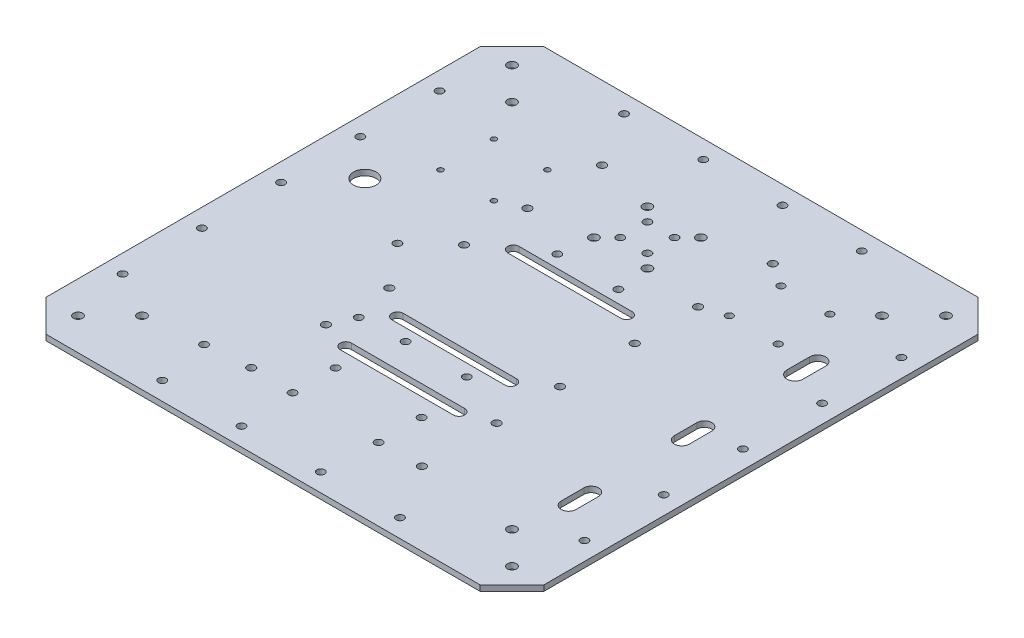
SolidWorks part; units mm, degrees
ref_plane "Front Plane" through (0, 0, 0) normal (0, 0, 1) x (1, 0, 0)
ref_plane "Top Plane" through (0, 0, 0) normal (0, 1, 0) x (1, 0, 0)
ref_plane "Right Plane" through (0, 0, 0) normal (1, 0, 0) x (0, 0, -1)
sketch "Sketch1" plane through (0, 0, 0) normal (0, 1, 0) x (1, 0, 0)
  line L0 (-160.4847, 61.5307) -> (-142.5242, 79.4912)
  line L1 (-160.4847, 79.4912) -> (118.9153, 79.4912)
  line L2 (-160.4847, 79.4912) -> (-160.4847, -199.9088)
  line L3 (-160.4847, -199.9088) -> (118.9153, -199.9088)
  line L4 (118.9153, 79.4912) -> (118.9153, -199.9088)
  line L5 (-20.7847, 79.4912) -> (-20.7847, -199.9088) construction
  line L6 (-160.4847, -60.2088) -> (118.9153, -60.2088) construction
  line L7 (118.9153, 61.5307) -> (100.9548, 79.4912)
  line L8 (118.9153, -181.9483) -> (100.9548, -199.9088)
  line L9 (-160.4847, -181.9483) -> (-142.5242, -199.9088)
  line L10 (-268.2478, 187.2542) -> (226.6783, -307.6719) construction
  line L11 (226.6783, -307.6719) -> (226.6783, 187.2542) construction
  line L12 (226.6783, 187.2542) -> (-268.2478, -307.6719) construction
  line L13 (-268.2478, -307.6719) -> (-268.2478, 187.2542) construction
  line L14 (-268.2478, 187.2542) -> (226.6783, 187.2542) construction
  line L15 (-268.2478, -307.6719) -> (226.6783, -307.6719) construction
  line L16 (-151.5045, 70.5109) -> (-268.2478, 187.2542) construction
  point P8 (-20.7847, 79.4912)
  point P11 (-160.4847, -60.2088)
  point P19 (118.9153, -60.2088)
  point P20 (-20.7847, -199.9088)
  point P22 (-151.5045, 70.5109)
  point P25 (-20.7847, -60.2088)
  point P26 (-20.7847, -60.2088)
  dimension "D1" = 279.4
  dimension "D2" = 279.4
  dimension "D3" = 165.1
  dimension "D4" = 25.4
extrude "Boss-Extrude1" add sketch "Sketch1" along normal blind 3.175 contours L2 L9 L3 L8 L4 L7 L1 L0 region at (-20.7847, 0, 60.2088)
sketch "Sketch2" plane through (0, 3.175, 0) normal (0, 1, 0) x (1, 0, 0)
  line L0 (-20.7847, 79.4912) -> (-20.7847, -287.8465) construction
  line L1 (-142.5242, 79.4912) -> (100.9548, 79.4912) construction
  line L2 (118.9153, -60.2088) -> (-158.2106, -60.2088) construction
  line L3 (118.9153, 61.5307) -> (118.9153, -181.9483) construction
  circle A0 centre (-38.0567, -17.5368) radius 2.159
  circle A1 centre (-3.7667, -17.5368) radius 2.159
  circle A2 centre (-38.0567, -102.6268) radius 2.159
  circle A3 centre (-3.7667, -102.6268) radius 2.159
  dimension "D5" = 4.318
  dimension "D6" = 4.318
  dimension "D7" = 4.318
  dimension "D8" = 4.318
  dimension "D1" = 17.272
  dimension "D2" = 34.29
  dimension "D3" = 85.09
  dimension "D4" = 42.672
extrude "Cut-Extrude1" cut sketch "Sketch2" against normal through all
sketch "Sketch4" plane through (0, 3.175, 0) normal (0, 1, 0) x (1, 0, 0)
  line L0 (-52.5347, -27.7088) -> (10.9653, -27.7088) construction
  line L1 (-52.5347, -24.5338) -> (10.9653, -24.5338)
  line L2 (-52.5347, -30.8838) -> (10.9653, -30.8838)
  line L3 (-52.5347, -92.7088) -> (10.9653, -92.7088) construction
  line L4 (-52.5347, -89.5338) -> (10.9653, -89.5338)
  line L5 (-52.5347, -95.8838) -> (10.9653, -95.8838)
  line L6 (118.9153, 61.5307) -> (118.9153, -181.9483) construction
  line L7 (-20.7847, -92.7088) -> (-20.7847, -198.1921) construction
  line L8 (-160.4847, -60.2088) -> (118.9153, -60.2088) construction
  line L9 (-160.4847, 61.5307) -> (-160.4847, -181.9483) construction
  line L14 (-52.5347, -121.708) -> (10.9653, -121.708) construction
  line L15 (-52.5347, -118.533) -> (10.9653, -118.533)
  line L16 (-52.5347, -124.883) -> (10.9653, -124.883)
  line L17 (-20.7847, -27.7088) -> (-20.7847, -92.7088) construction
  arc A0 (-52.5347, -24.5338) -> (-52.5347, -30.8838) centre (-52.5347, -27.7088) ccw
  arc A1 (10.9653, -30.8838) -> (10.9653, -24.5338) centre (10.9653, -27.7088) ccw
  arc A2 (-52.5347, -89.5338) -> (-52.5347, -95.8838) centre (-52.5347, -92.7088) ccw
  arc A3 (10.9653, -95.8838) -> (10.9653, -89.5338) centre (10.9653, -92.7088) ccw
  arc A7 (-52.5347, -118.533) -> (-52.5347, -124.883) centre (-52.5347, -121.708) ccw
  arc A8 (10.9653, -124.883) -> (10.9653, -118.533) centre (10.9653, -121.708) ccw
  point P2 (-20.7847, -27.7088)
  point P7 (-20.7847, -92.7088)
  point P18 (-20.7847, -60.2088)
  point P19 (-20.7847, -60.2088)
  point P33 (-20.7847, -121.708)
  dimension "D1" = 63.5
  dimension "D2" = 63.5
  dimension "D3" = 6.35
  dimension "D4" = 6.35
  dimension "D5" = 65
  dimension "D6" = 28.9992
  dimension "D8" = 63.5
  dimension "D9" = 6.35
extrude "Cut-Extrude2" cut sketch "Sketch4" against normal through all
sketch "Sketch7" plane through (0, 3.175, 0) normal (0, 1, 0) x (1, 0, 0)
  line L0 (-96.7307, 89.5196) -> (-96.7307, -24.0818) construction
  line L1 (-160.4847, -60.2088) -> (118.9153, -60.2088) construction
  line L2 (-160.4847, 61.5307) -> (-160.4847, -181.9483) construction
  line L3 (118.9153, 61.5307) -> (118.9153, -181.9483) construction
  line L4 (-20.7847, 79.4912) -> (-20.7847, -252.674) construction
  line L5 (-142.5242, 79.4912) -> (100.9548, 79.4912) construction
  circle A0 centre (-81.7447, 20.5632) radius 1.524
  circle A1 centre (-81.7447, -9.4088) radius 1.524
  circle A2 centre (-111.7167, -9.4088) radius 1.524
  circle A3 centre (-111.7167, 20.5632) radius 1.524
  dimension "D1" = 3.048
  dimension "D2" = 14.986
  dimension "D4" = 29.972
  dimension "D3" = 3.048
  dimension "D5" = 50.8
  dimension "D6" = 60.96
  dimension "D7" = 14.986
extrude "Cut-Extrude3" cut sketch "Sketch7" against normal through all
sketch "Sketch8" plane through (0, 3.175, 0) normal (0, 1, 0) x (1, 0, 0)
  line L0 (-142.5242, -199.9088) -> (100.9548, -199.9088) construction
  line L1 (118.9153, 61.5307) -> (118.9153, -181.9483) construction
  circle A0 centre (8.4253, -175.0168) radius 1.524
  circle A1 centre (8.4253, -144.5368) radius 1.524
  circle A2 centre (32.3013, -175.0168) radius 1.524
  circle A3 centre (32.3013, -144.5368) radius 1.524
  dimension "D1" = 3.048
  dimension "D2" = 30.48
  dimension "D3" = 23.876
  dimension "D4" = 24.892
  dimension "D5" = 86.614
extrude "Cut-Extrude4" [suppressed] cut sketch "Sketch8" against normal through all and the other way through all
sketch "Sketch10" plane through (0, 0, 0) normal (0, -1, 0) x (1, 0, 0)
  line L0 (-142.5242, 199.9088) -> (100.9548, 199.9088) construction
  line L1 (-20.7847, 199.9088) -> (-20.7847, 128.7119) construction
  line L2 (-52.5347, 124.883) -> (10.9653, 124.883) construction
  circle A0 centre (-44.9147, 159.173) radius 2.159
  circle A1 centre (3.3453, 159.173) radius 2.159
  circle A2 centre (-44.9147, 135.043) radius 2.159
  circle A3 centre (3.3453, 135.043) radius 2.159
  dimension "D1" = 4.318
  dimension "D2" = 48.26
  dimension "D4" = 10.16
  dimension "D6" = 4.318
  dimension "D7" = 4.318
  dimension "D8" = 4.318
  dimension "D3" = 24.13
  dimension "D5" = 24.13
extrude "Cut-Extrude6" cut sketch "Sketch10" against normal through all
sketch "Sketch9" plane through (0, 0, 0) normal (0, -1, 0) x (-1, 0, 0)
  line L1 (160.4847, -60.2088) -> (-327.4314, -60.2088) construction
  line L2 (-53.8913, -43.6513) -> (-53.8913, -126.5783) construction
  line L3 (20.7847, 79.4912) -> (20.7847, -331.7119) construction
  line L4 (142.5242, 79.4912) -> (-100.9548, 79.4912) construction
  line L7 (160.4847, 61.5307) -> (160.4847, -181.9483) construction
  circle A0 centre (-40.1753, 0.7512) radius 2.032
  circle A1 centre (-67.6073, 0.7512) radius 2.032
  circle A2 centre (-40.1753, 29.7072) radius 2.032
  circle A3 centre (-67.6073, 29.7072) radius 2.032
  dimension "D1" = 4.064
  dimension "D9" = 4.064
  dimension "D2" = 60.96
  dimension "D3" = 28.956
  dimension "D4" = 60.96
  dimension "D8" = 13.716
extrude "Cut-Extrude5" cut sketch "Sketch9" against normal through all
sketch "Sketch13" plane through (0, 0, 0) normal (0, -1, 0) x (1, 0, 0)
  line L0 (-20.7847, -79.4912) -> (-20.7847, 261.4711) construction
  line L1 (-142.5242, -79.4912) -> (100.9548, -79.4912) construction
  line L2 (-160.4847, 60.2088) -> (239.2508, 60.2088) construction
  line L3 (-160.4847, -61.5307) -> (-160.4847, 181.9483) construction
  line L4 (-35.7847, -30.7512) -> (-35.7847, -0.7512) construction
  line L5 (-35.7847, -15.7512) -> (8.2736, -15.7512) construction
  circle A0 centre (-35.7847, -0.7512) radius 2.54
  circle A1 centre (-35.7847, -30.7512) radius 2.54
  circle A2 centre (-5.7847, -30.7512) radius 2.54
  circle A3 centre (-5.7847, -0.7512) radius 2.54
  circle A4 centre (-28.4047, -23.3712) radius 2.159
  circle A5 centre (-28.4047, -8.1312) radius 2.159
  circle A6 centre (-13.1647, -8.1312) radius 2.159
  circle A7 centre (-13.1647, -23.3712) radius 2.159
  dimension "D1" = 5.08
  dimension "D2" = 5.08
  dimension "D6" = 4.318
  dimension "D7" = 15.24
  dimension "D3" = 30
  dimension "D4" = 15
  dimension "D5" = 60.96
  dimension "D8" = 15.24
extrude "Cut-Extrude8" cut sketch "Sketch13" against normal through all
sketch "Sketch14" plane through (0, 0, 0) normal (0, -1, 0) x (1, 0, 0)
  line L0 (-20.7847, 199.9088) -> (-20.7847, -154.5354) construction
  line L1 (-142.5242, 199.9088) -> (100.9548, 199.9088) construction
  line L2 (-160.4847, 60.2088) -> (331.9066, 60.2088) construction
  line L3 (-160.4847, -61.5307) -> (-160.4847, 181.9483) construction
  line L4 (-160.4847, 181.9483) -> (-142.5242, 199.9088) construction
  line L5 (-268.2478, -187.2542) -> (226.6783, 307.6719) construction
  line L6 (-268.2478, -187.2542) -> (226.6783, -187.2542) construction
  line L7 (-268.2478, -187.2542) -> (-268.2478, 307.6719) construction
  line L8 (-160.4847, 181.9483) -> (-142.5242, 199.9088) construction
  line L9 (-151.5045, 190.9286) -> (-83.1439, 122.568) construction
  line L10 (-268.2478, 307.6719) -> (226.6783, 307.6719) construction
  line L11 (226.6783, -187.2542) -> (226.6783, 307.6719) construction
  line L12 (226.6783, -187.2542) -> (-268.2478, 307.6719) construction
  line L14 (-160.4847, -61.5307) -> (-142.5242, -79.4912) construction
  line L21 (-268.2478, -187.2542) -> (-151.5045, -70.5109) construction
  line L22 (109.935, -70.5109) -> (226.6783, -187.2542) construction
  line L23 (118.9153, -61.5307) -> (100.9548, -79.4912) construction
  line L24 (109.935, 190.9286) -> (226.6783, 307.6719) construction
  line L25 (118.9153, 181.9483) -> (100.9548, 199.9088) construction
  line L26 (-268.2478, 307.6719) -> (-151.5045, 190.9286) construction
  circle A1 centre (-142.5242, 181.9483) radius 2.54
  circle A3 centre (-124.5637, 163.9878) radius 2.54
  circle A4 centre (82.9942, 163.9878) radius 2.54
  circle A7 centre (100.9548, 181.9483) radius 2.54
  circle A8 centre (-142.5242, -61.5307) radius 2.54
  circle A11 centre (-124.5637, -43.5701) radius 2.54
  circle A14 centre (100.9548, -61.5307) radius 2.54
  circle A15 centre (82.9942, -43.5701) radius 2.54
  point P8 (-20.7847, 60.2088)
  point P30 (226.6783, 60.2088)
  point P33 (-151.5045, -70.5109)
  point P36 (-20.7847, -187.2542)
  dimension "D3" = 5.08
  dimension "D6" = 5.08
  dimension "D1" = 12.7
  dimension "D2" = 165.1
  dimension "D9" = 25.4
extrude "Cut-Extrude9" cut sketch "Sketch14" against normal through all
sketch "Sketch15" plane through (0, 0, 0) normal (0, -1, 0) x (1, 0, 0)
  line L0 (-20.7847, 199.9088) -> (-20.7847, 125.875) construction
  line L1 (-142.5242, 199.9088) -> (100.9548, 199.9088) construction
  line L2 (-160.4847, 60.2088) -> (75.4631, 60.2088) construction
  line L3 (-160.4847, -61.5307) -> (-160.4847, 181.9483) construction
  circle A0 centre (-43.0097, 189.7488) radius 2.159
  circle A1 centre (-87.4597, 189.7488) radius 2.159
  circle A2 centre (-150.3247, 60.2088) radius 2.159
  circle A3 centre (-150.3247, 104.6588) radius 2.159
  circle A4 centre (-150.3247, 149.1088) radius 2.159
  circle A5 centre (108.7553, 149.1088) radius 2.159
  circle A6 centre (108.7553, 104.6588) radius 2.159
  circle A7 centre (108.7553, 60.2088) radius 2.159
  circle A8 centre (45.8903, 189.7488) radius 2.159
  circle A9 centre (1.4403, 189.7488) radius 2.159
  circle A10 centre (1.4403, -69.3312) radius 2.159
  circle A11 centre (45.8903, -69.3312) radius 2.159
  circle A12 centre (108.7553, 15.7588) radius 2.159
  circle A13 centre (108.7553, -28.6912) radius 2.159
  circle A14 centre (-150.3247, -28.6912) radius 2.159
  circle A15 centre (-150.3247, 15.7588) radius 2.159
  circle A16 centre (-87.4597, -69.3312) radius 2.159
  circle A17 centre (-43.0097, -69.3312) radius 2.159
  dimension "D3" = 4.318
  dimension "D4" = 4.318
  dimension "D8" = 4.318
  dimension "D9" = 4.318
  dimension "D10" = 4.318
  dimension "D1" = 22.225
  dimension "D2" = 44.45
  dimension "D5" = 10.16
  dimension "D6" = 44.45
  dimension "D7" = 44.45
  dimension "D11" = 10.16
extrude "Cut-Extrude10" cut sketch "Sketch15" against normal through all
sketch "Sketch16" plane through (0, 0, 0) normal (0, -1, 0) x (-1, 0, 0)
  line L0 (20.7847, 79.4912) -> (20.7847, -323.0503) construction
  line L1 (-49.3193, -131.0748) -> (-89.9593, -131.0748)
  line L2 (-49.3193, -131.0748) -> (-49.3193, -47.5088)
  line L3 (-49.3193, -47.5088) -> (-89.9593, -47.5088)
  line L4 (-89.9593, -131.0748) -> (-89.9593, -47.5088)
  line L5 (131.5287, -131.0748) -> (131.5287, -47.5088)
  line L6 (142.5242, 79.4912) -> (-100.9548, 79.4912) construction
  line L7 (160.4847, -60.2088) -> (-312.3855, -60.2088) construction
  line L8 (160.4847, 61.5307) -> (160.4847, -181.9483) construction
  line L9 (90.8887, -47.5088) -> (131.5287, -47.5088)
  line L10 (90.8887, -131.0748) -> (90.8887, -47.5088)
  line L11 (90.8887, -131.0748) -> (131.5287, -131.0748)
  circle A0 centre (-74.7193, -140.9808) radius 2.159
  circle A1 centre (-69.6393, -37.6028) radius 2.159
  circle A2 centre (-99.8653, -84.4248) radius 2.159
  circle A3 centre (141.4347, -84.4248) radius 2.159
  circle A4 centre (111.2087, -37.6028) radius 2.159
  circle A5 centre (116.2887, -140.9808) radius 2.159
  dimension "D3" = 9.906
  dimension "D4" = 9.906
  dimension "D5" = 9.906
  dimension "D6" = 15.24
  dimension "D7" = 20.32
  dimension "D8" = 46.65
  dimension "D9" = 4.318
  dimension "D10" = 4.318
  dimension "D11" = 4.318
  dimension "D1" = 83.566
  dimension "D2" = 40.64
  dimension "D12" = 120.65
  dimension "D13" = 12.7
extrude "Cut-Extrude11" [suppressed] cut sketch "Sketch16" against normal through all contours A5 | A3 | A4
sketch "Sketch17" plane through (0, 3.175, 0) normal (0, 1, 0) x (1, 0, 0)
  line L2 (-20.7847, 79.4912) -> (-20.7847, -395.818) construction
  line L3 (-142.5242, 79.4912) -> (100.9548, 79.4912) construction
  line L4 (118.9153, -60.2088) -> (-127.1454, -60.2088) construction
  line L5 (118.9153, 61.5307) -> (118.9153, -181.9483) construction
  circle A12 centre (27.0943, -158.6338) radius 2.2225
  circle A13 centre (-68.6637, -158.6338) radius 2.2225
  circle A14 centre (27.0943, -116.7238) radius 2.2225
  circle A15 centre (-68.6637, -116.7238) radius 2.2225
  circle A16 centre (27.0943, -81.1638) radius 2.2225
  circle A17 centre (-68.6637, -81.1638) radius 2.2225
  circle A18 centre (27.0943, -39.2538) radius 2.2225
  circle A19 centre (-68.6637, -39.2538) radius 2.2225
  circle A20 centre (27.0943, -3.6938) radius 2.2225
  circle A21 centre (-68.6637, -3.6938) radius 2.2225
  circle A22 centre (27.0943, 38.2162) radius 2.2225
  circle A23 centre (-68.6637, 38.2162) radius 2.2225
  circle A24 centre (-68.6637, 38.2162) radius 2.2225
  circle A25 centre (27.0943, 38.2162) radius 2.2225
  circle A26 centre (-68.6637, -3.6938) radius 2.2225
  circle A27 centre (27.0943, -3.6938) radius 2.2225
  circle A28 centre (-68.6637, -39.2538) radius 2.2225
  circle A29 centre (27.0943, -39.2538) radius 2.2225
  circle A30 centre (-68.6637, -81.1638) radius 2.2225
  circle A31 centre (27.0943, -81.1638) radius 2.2225
  circle A32 centre (-68.6637, -116.7238) radius 2.2225
  circle A33 centre (27.0943, -116.7238) radius 2.2225
  circle A34 centre (-68.6637, -158.6338) radius 2.2225
  dimension "D1" = 4.445
  dimension "D2" = 4.445
  dimension "D3" = 4.445
  dimension "D4" = 4.445
  dimension "D5" = 4.445
  dimension "D6" = 4.445
  dimension "D7" = 4.445
  dimension "D8" = 4.445
  dimension "D9" = 4.445
  dimension "D10" = 4.445
  dimension "D11" = 4.445
  dimension "D12" = 4.445
  dimension "D25" = 56.515
  dimension "D24" = 56.515
  dimension "D13" = 95.758
  dimension "D14" = 41.91
  dimension "D15" = 95.758
  dimension "D16" = 41.91
  dimension "D17" = 95.758
  dimension "D18" = 41.91
  dimension "D19" = 47.879
  dimension "D20" = 47.879
  dimension "D21" = 47.879
  dimension "D22" = 20.955
extrude "Cut-Extrude13" cut sketch "Sketch17" against normal through all contours A23 | A22 | A20 | A21 | A18 | A19 | A17 | A16 | A12 | A14 | A15 | A13
sketch "Sketch18" [suppressed] plane through (0, 3.175, 0) normal (0, 1, 0) x (1, 0, 0)
  line L1 (-142.5242, -199.9088) -> (-160.4847, -181.9483)
  line L2 (-142.5242, -199.9088) -> (-106.6032, -163.9878)
  line L3 (-106.6032, -163.9878) -> (-124.5637, -146.0273)
  line L4 (-160.4847, -181.9483) -> (-124.5637, -146.0273)
  line L5 (-20.7847, 79.4912) -> (-20.7847, -264.9481) construction
  line L6 (-142.5242, 79.4912) -> (100.9548, 79.4912) construction
  line L7 (118.9153, -60.2088) -> (-155.4453, -60.2088) construction
  line L8 (118.9153, 61.5307) -> (118.9153, -181.9483) construction
  line L9 (-160.4847, 61.5307) -> (-124.5637, 25.6096)
  line L10 (-106.6032, 43.5701) -> (-124.5637, 25.6096)
  line L11 (-142.5242, 79.4912) -> (-106.6032, 43.5701)
  line L12 (-142.5242, 79.4912) -> (-160.4847, 61.5307)
  line L13 (100.9548, 79.4912) -> (118.9153, 61.5307)
  line L14 (100.9548, 79.4912) -> (65.0337, 43.5701)
  line L15 (65.0337, 43.5701) -> (82.9942, 25.6096)
  line L16 (118.9153, 61.5307) -> (82.9942, 25.6096)
  line L17 (118.9153, -181.9483) -> (82.9942, -146.0273)
  line L18 (65.0337, -163.9878) -> (82.9942, -146.0273)
  line L19 (100.9548, -199.9088) -> (65.0337, -163.9878)
  line L20 (100.9548, -199.9088) -> (118.9153, -181.9483)
  line L21 (-142.5242, -181.9483) -> (-124.5637, -163.9878) construction
  line L22 (-160.4847, -181.9483) -> (-142.5242, -199.9088) construction
  line L23 (-160.4847, -181.9483) -> (-142.5242, -199.9088) construction
  circle A2 centre (-124.5637, -163.9878) radius 2.54 construction
  circle A3 centre (-142.5242, -181.9483) radius 2.54 construction
  circle A4 centre (-124.5637, -163.9878) radius 2.54 construction
  circle A5 centre (-142.5242, -181.9483) radius 2.54 construction
  point P12 (-151.5045, -190.9286)
  point P33 (-151.5045, -190.9286)
  dimension "D1" = 50.8
  dimension "D2" = 25.4
sketch "Sketch19" plane through (0, 3.175, 0) normal (0, 1, 0) x (1, 0, 0)
  line L0 (87.1653, -136.4088) -> (87.1653, -123.7088) construction
  line L1 (83.0169, -136.4088) -> (83.0169, -123.7088)
  line L2 (91.3137, -136.4088) -> (91.3137, -123.7088)
  line L3 (87.1653, -72.9088) -> (87.1653, -60.2088) construction
  line L4 (83.0169, -72.9088) -> (83.0169, -60.2088)
  line L5 (91.3137, -72.9088) -> (91.3137, -60.2088)
  line L6 (87.1653, -9.4088) -> (87.1653, 3.2912) construction
  line L7 (82.6711, -9.4088) -> (82.6711, 3.2912)
  line L8 (91.6594, -9.4088) -> (91.6594, 3.2912)
  line L9 (118.9153, 61.5307) -> (118.9153, -181.9483) construction
  line L10 (-142.5242, -199.9088) -> (100.9548, -199.9088) construction
  arc A0 (83.0169, -136.4088) -> (91.3137, -136.4088) centre (87.1653, -136.4088) ccw
  arc A1 (91.3137, -123.7088) -> (83.0169, -123.7088) centre (87.1653, -123.7088) ccw
  arc A2 (83.0169, -72.9088) -> (91.3137, -72.9088) centre (87.1653, -72.9088) ccw
  arc A3 (91.3137, -60.2088) -> (83.0169, -60.2088) centre (87.1653, -60.2088) ccw
  arc A4 (82.6711, -9.4088) -> (91.6594, -9.4088) centre (87.1653, -9.4088) ccw
  arc A5 (91.6594, 3.2912) -> (82.6711, 3.2912) centre (87.1653, 3.2912) ccw
  point P2 (87.1653, -130.0588)
  point P7 (87.1653, -66.5588)
  point P14 (87.1653, -3.0588)
  dimension "D1" = 12.7
  dimension "D2" = 12.7
  dimension "D3" = 12.7
  dimension "D4" = 50.8
  dimension "D5" = 50.8
  dimension "D6" = 31.75
  dimension "D7" = 63.5
extrude "Cut-Extrude14" cut sketch "Sketch19" against normal through all
sketch "Sketch20" plane through (0, 3.175, 0) normal (0, 1, 0) x (1, 0, 0)
  line L0 (-160.4847, -60.2088) -> (142.2929, -60.2088) construction
  line L1 (-160.4847, 61.5307) -> (-160.4847, -181.9483) construction
  line L2 (-20.7847, 79.4912) -> (-20.7847, -217.6785) construction
  line L3 (-142.5242, 79.4912) -> (100.9548, 79.4912) construction
  circle A0 centre (-128.7347, -34.8088) radius 6.35
  dimension "D1" = 12.7
  dimension "D3" = 25.4
  dimension "D2" = 31.75
extrude "Cut-Extrude15" cut sketch "Sketch20" against normal through all
sketch "Sketch22" plane through (0, 3.175, 0) normal (0, 1, 0) x (1, 0, 0)
  line L0 (-62.9487, -104.0291) -> (-93.1747, -104.0291) construction
  line L1 (-93.1747, -104.0291) -> (-93.1747, -160.5847) construction
  line L2 (-88.0947, -104.0291) -> (-88.0947, -57.2067) construction
  line L3 (-68.6637, -81.1638) -> (-68.6637, -116.7238) construction
  circle A0 centre (-88.0947, -57.2067) radius 2.159
  circle A1 centre (-62.9487, -104.0291) radius 2.159
  circle A2 centre (-93.1747, -160.5847) radius 2.159
  dimension "D5" = 4.318
  dimension "D6" = 5.715
  dimension "D1" = 25.146
  dimension "D2" = 5.08
  dimension "D3" = 46.8224
  dimension "D4" = 56.5556
extrude "Cut-Extrude16" cut sketch "Sketch22" against normal through all
